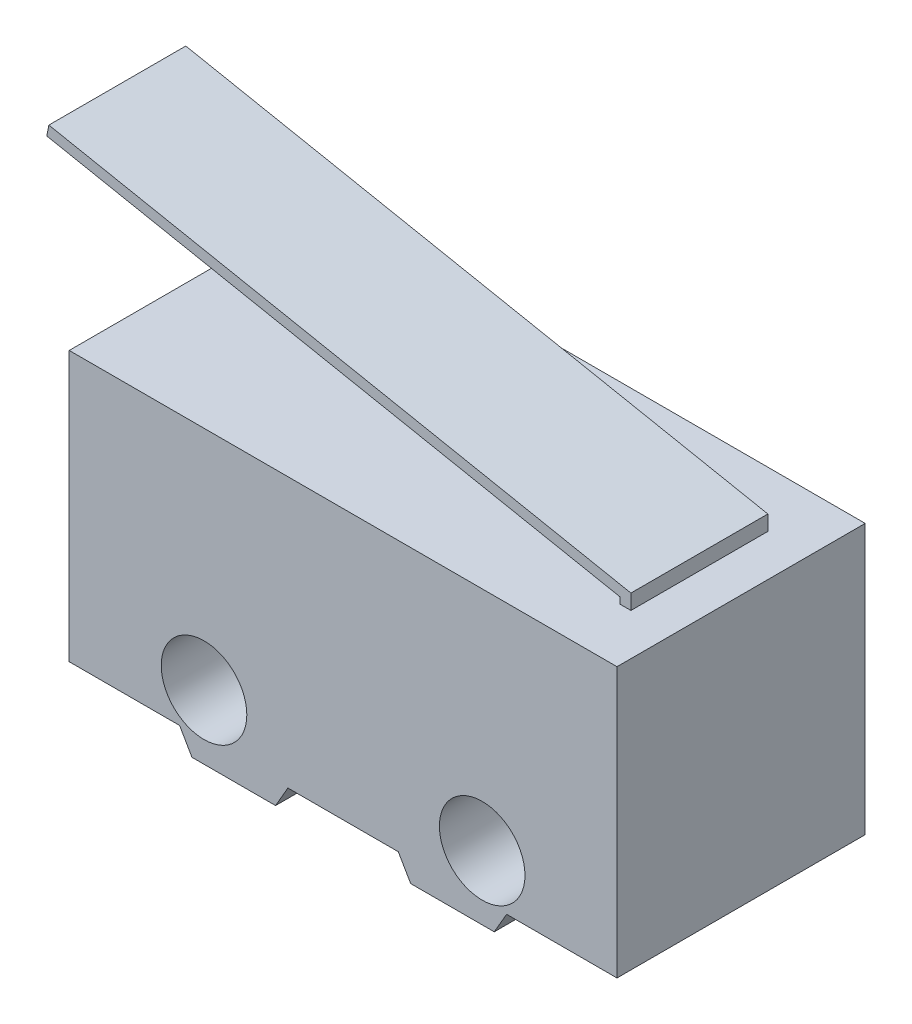
SolidWorks part; units mm, degrees
ref_plane "Front Plane" through (0, 0, 0) normal (0, 0, 1) x (1, 0, 0)
ref_plane "Top Plane" through (0, 0, 0) normal (0, 1, 0) x (1, 0, 0)
ref_plane "Right Plane" through (0, 0, 0) normal (1, 0, 0) x (0, 0, -1)
sketch "Sketch1" plane through (0, 0, 0) normal (0, 0, 1) x (1, 0, 0)
  line L1 (6.4, 3.15) -> (-6.4, 3.15)
  line L2 (6.4, 3.15) -> (6.4, -3.15)
  line L3 (6.4, -3.15) -> (-6.4, -3.15)
  line L4 (-6.4, 3.15) -> (-6.4, -3.15)
  line L5 (6.4, 3.15) -> (-6.4, -3.15) construction
  line L6 (6.4, -3.15) -> (-6.4, 3.15) construction
  point P0 (0, 0)
  dimension "D1" = 12.8
  dimension "D2" = 6.3
extrude "Boss-Extrude1" add sketch "Sketch1" along normal mid plane 5.8
sketch "Sketch2" plane through (0, 0, 2.9) normal (0, 0, 1) x (1, 0, 0)
  line L0 (0, 0) -> (0, -3.15) construction
  line L1 (-6.4, -3.15) -> (6.4, -3.15) construction
  line L2 (0, -3.15) -> (0, 0) construction
  line L5 (-4.5087, -1.9581) -> (-3.532, -0.2663)
  line L6 (3.532, -0.2663) -> (1.5784, -0.2663)
  line L7 (1.5784, -0.2663) -> (0.6016, -1.9581)
  line L8 (0.6016, -1.9581) -> (1.5784, -3.65)
  line L9 (1.5784, -3.65) -> (3.532, -3.65)
  line L10 (3.532, -3.65) -> (4.5087, -1.9581)
  line L11 (4.5087, -1.9581) -> (3.532, -0.2663)
  line L12 (-3.532, -3.65) -> (-4.5087, -1.9581)
  line L13 (-1.5784, -3.65) -> (-3.532, -3.65)
  line L14 (-0.6016, -1.9581) -> (-1.5784, -3.65)
  line L15 (-1.5784, -0.2663) -> (-0.6016, -1.9581)
  line L16 (-3.532, -0.2663) -> (-1.5784, -0.2663)
  line L17 (-6.4, -3.15) -> (-3.8206, -3.15) construction
  line L18 (-1.2897, -3.15) -> (1.2897, -3.15) construction
  line L19 (3.8206, -3.15) -> (6.4, -3.15) construction
  circle A0 centre (3.25, -2.15) radius 1
  circle A1 centre (-3.25, -2.15) radius 1
  circle A2 centre (2.5552, -1.9581) radius 1.6919 construction
  circle A3 centre (-2.5552, -1.9581) radius 1.6919 construction
  point P8 (1.2897, -3.15)
  point P16 (3.8206, -3.15)
  point P33 (-3.8206, -3.15)
  point P34 (-1.2897, -3.15)
  dimension "D1" = 6.5
  dimension "D2" = 2
  dimension "D3" = 1.5
  dimension "D4" = 1.9536
extrude "Boss-Extrude3" add sketch "Sketch2" against normal through all contours L6 L7 L8 L9 L10 L11 | L5 L16 L15 L14 L13 L12
extrude "Cut-Extrude2" cut sketch "Sketch2<3>" against normal through all contours A1 | A0
sketch "Sketch2<3>" plane through (0, 0, 2.9) normal (0, 0, 1) x (1, 0, 0) same geometry as "Sketch2"
sketch "Sketch3" plane through (0, 0, 0) normal (0, 0, 1) x (1, 0, 0)
  line L0 (5.3, 3.4) -> (-8.2, 6.05)
  line L1 (6.4, -3.15) -> (6.4, 3.15) construction
  line L4 (6.4, 3.15) -> (-6.4, 3.15) construction
  line L5 (5.3, 3.4) -> (5.3, 3.15)
  circle A0 centre (3.25, -2.15) radius 1 construction
  dimension "D3" = 8.2
  dimension "D5" = 11.45
  dimension "D1" = 1.1
  dimension "D4" = 0.25
extrude "Extrude-Thin1" add sketch "Sketch3" along normal mid plane 3.2 thin thin type mid plane wall 0.25
